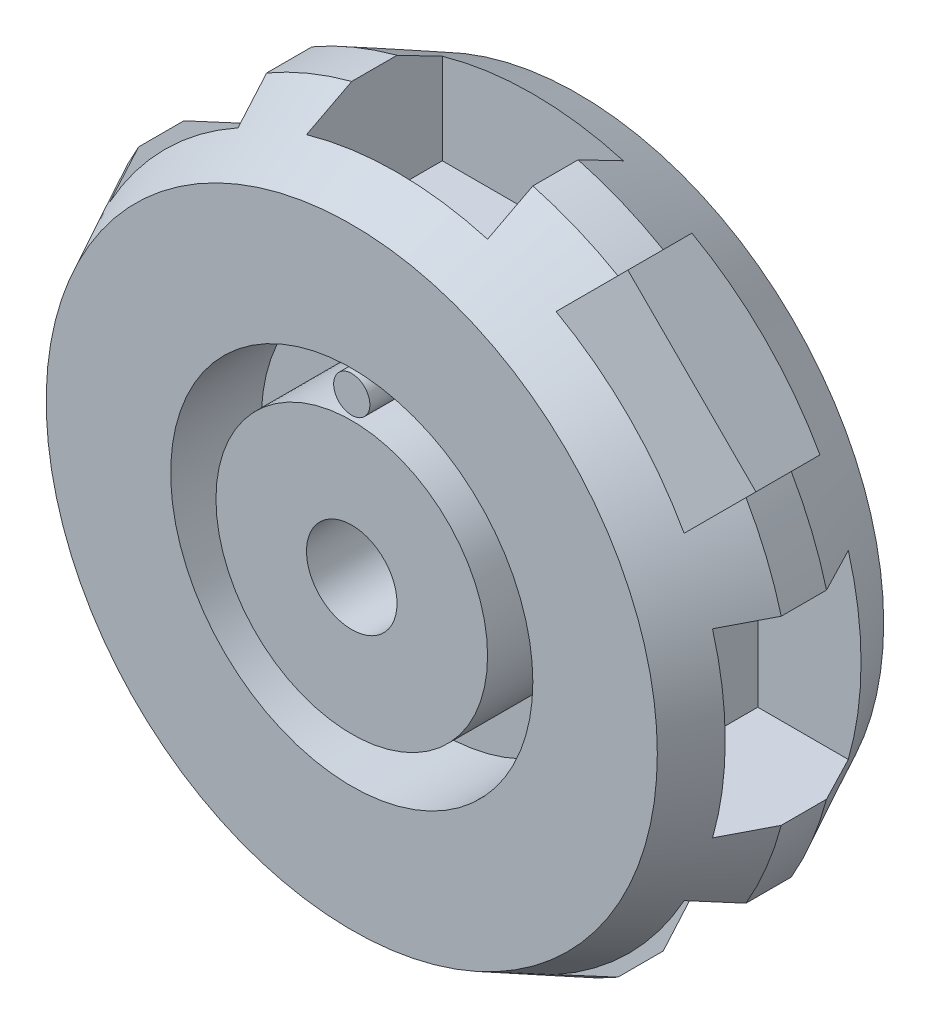
SolidWorks part; units mm, degrees
ref_plane "Front Plane" through (0, 0, 0) normal (0, 0, 1) x (1, 0, 0)
ref_plane "Top Plane" through (0, 0, 0) normal (0, 1, 0) x (1, 0, 0)
ref_plane "Right Plane" through (0, 0, 0) normal (1, 0, 0) x (0, 0, -1)
sketch "Sketch1" plane through (0, 0, 0) normal (0, 0, 1) x (1, 0, 0)
  circle A0 centre (0, 0) radius 24.6062
  circle A1 centre (0, 0) radius 3.175
  dimension "D1" = 49.2125
  dimension "D2" = 6.35
extrude "Boss-Extrude1" add sketch "Sketch1" along normal blind 15.875
sketch "Sketch2" plane through (0, 0, 15.875) normal (0, 0, 1) x (1, 0, 0)
  circle A0 centre (0, 0) radius 9.525
  circle A1 centre (0, 0) radius 12.7
  dimension "D1" = 19.05
  dimension "D2" = 3.175
extrude "Cut-Extrude1" cut sketch "Sketch2" against normal blind 6.35
sketch "Sketch4" plane through (0, 0, 0) normal (0, 0, -1) x (-1, 0, 0)
  circle A0 centre (0, 0) radius 9.525
  circle A1 centre (0, 0) radius 12.7
  dimension "D1" = 19.05
  dimension "D2" = 3.175
extrude "Cut-Extrude3" cut sketch "Sketch4" against normal blind 6.35
ref_axis "Axis1" through (0, 0, 15.875) along (0, 0, -1)
chamfer "Chamfer1" distance 3.175 distance2 6.35 1 edges at (24.6063, 0, 0) first distance on face at (-12.7, 0, 0)
chamfer "Chamfer2" distance 6.35 distance2 3.175 1 edges at (24.6063, 0, 15.875) first distance on face at (24.6063, 0, 6.35)
sketch "Sketch5" plane through (0, 0, 0) normal (0, 0, -1) x (-1, 0, 0)
  line L0 (0, 23.0188) -> (0, 19.7513) construction
  line L2 (-6.35, 26.2862) -> (6.35, 26.2862)
  line L3 (-6.35, 26.2862) -> (-6.35, 22.1256)
  line L5 (6.35, 26.2862) -> (6.35, 22.1256)
  line L6 (-6.35, 26.2862) -> (0, 23.0188) construction
  line L7 (0, 23.0188) -> (6.35, 26.2862) construction
  arc A0 (6.35, 22.1256) -> (-6.35, 22.1256) centre (0, 0) ccw
  dimension "D1" = 46.0375
  dimension "D2" = 12.7
extrude "Cut-Extrude5" cut sketch "Sketch5" against normal through all contours L2 L5 A0 L3
pattern_circular "CirPattern2" count 8 over 360 about axis through (0, 0, 15.875) along (0, 0, -1) of "Cut-Extrude5"
sketch "Sketch6" plane through (0, 0, 6.35) normal (0, 0, -1) x (-1, 0, 0)
  line L0 (0, -9.525) -> (0, -12.7) construction
  circle A0 centre (0, 0) radius 9.525 construction
  circle A1 centre (0, 0) radius 9.525 construction
  circle A2 centre (0, 0) radius 12.7 construction
  circle A3 centre (0, -11.1125) radius 1.27
  dimension "D1" = 2.54
extrude "Boss-Extrude2" add sketch "Sketch6" along normal blind 6.35 contours A3
sketch "Sketch9" plane through (0, 0, 9.525) normal (0, 0, 1) x (1, 0, 0)
  line L0 (0, 9.525) -> (0, 12.7) construction
  circle A0 centre (0, 0) radius 9.525 construction
  circle A1 centre (0, 0) radius 9.525 construction
  circle A2 centre (0, 0) radius 12.7 construction
  circle A3 centre (0, 11.1125) radius 1.27
  dimension "D1" = 2.54
extrude "Boss-Extrude3" add sketch "Sketch9" along normal blind 6.35 contours A3
sketch "Sketch14" plane through (6.35, 0, 0) normal (-1, 0, 0) x (0, 0, 1)
  line L0 (6.35, 23.7728) -> (9.525, 23.7728)
  line L1 (9.525, 23.7728) -> (12.7, 22.1256)
  line L2 (12.7, 22.1256) -> (3.175, 22.1256)
  line L3 (3.175, 22.1256) -> (6.35, 23.7728)
  spline S0 degree 3 poles (12.7, 22.1256) (11.6423, 22.6758) (10.5839, 23.2248) (9.525, 23.7728) knots 0 0 0 0 1 1 1 1 construction
  spline S1 degree 3 poles (6.35, 23.7728) (5.2911, 23.2248) (4.2327, 22.6758) (3.175, 22.1256) knots 0 0 0 0 1 1 1 1 construction
extrude "Cut-Extrude6" cut sketch "Sketch14" along normal up to next
pattern_circular "CirPattern3" count 8 over 360 about axis through (0, 0, 15.875) along (0, 0, -1) of "Cut-Extrude6"
sketch "Sketch16" plane through (0, 22.1256, 0) normal (0, 1, 0) x (1, 0, 0)
  line L1 (-6.35, -12.7) -> (6.35, -12.7)
  line L2 (-6.35, -12.7) -> (-6.35, -3.175)
  line L3 (-6.35, -3.175) -> (6.35, -3.175)
  line L4 (6.35, -12.7) -> (6.35, -3.175)
extrude "Cut-Extrude7" cut sketch "Sketch16" against normal blind 6.35 and the other way blind 6.35
pattern_circular "CirPattern4" count 8 over 360 about axis through (0, 0, 15.875) along (0, 0, -1) of "Cut-Extrude7"
